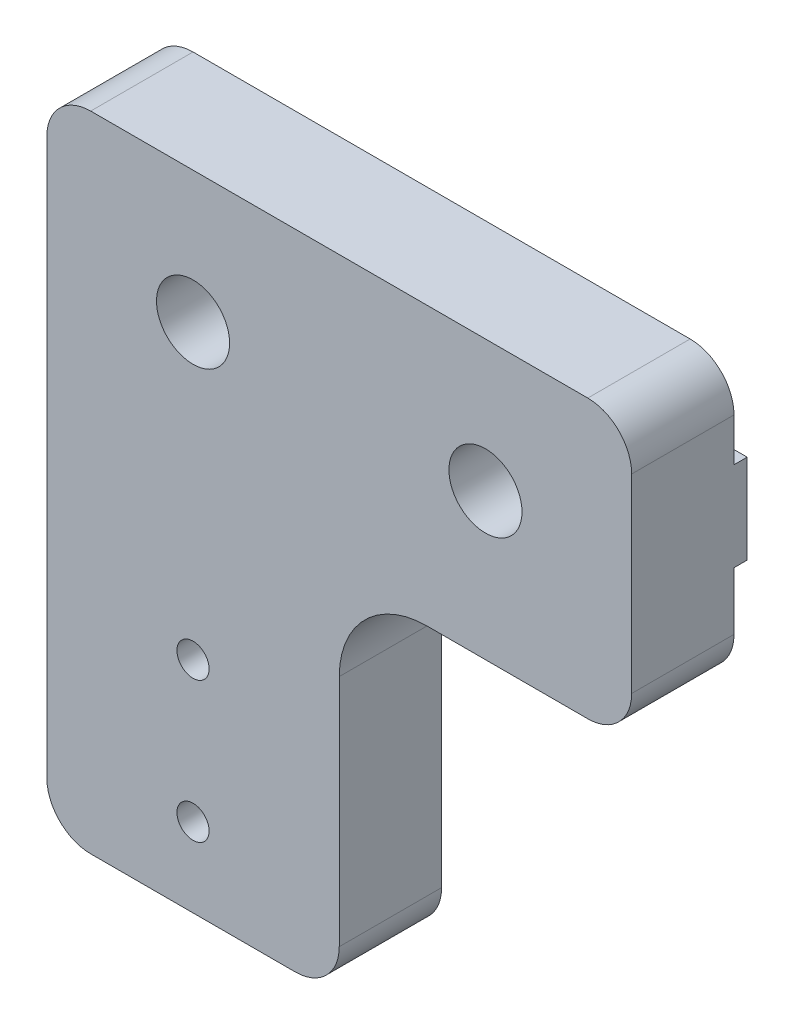
SolidWorks part; units mm, degrees
material "ABS"
ref_plane "Front Plane" through (0, 0, 0) normal (0, 0, 1) x (1, 0, 0)
ref_plane "Top Plane" through (0, 0, 0) normal (0, 1, 0) x (1, 0, 0)
ref_plane "Right Plane" through (0, 0, 0) normal (1, 0, 0) x (0, 0, -1)
sketch "Sketch1" plane through (0, 0, 0) normal (0, 0, 1) x (1, 0, 0)
  line L0 (3, 0) -> (17, 0)
  line L1 (20, 3) -> (20, 19)
  line L2 (26, 25) -> (37, 25)
  line L3 (40, 28) -> (40, 41)
  line L4 (37, 44) -> (3, 44)
  line L5 (0, 41) -> (0, 3)
  line L6 (0, 35) -> (40, 35) construction
  line L7 (20, 25) -> (20, 44) construction
  line L8 (10, 0) -> (10, 44) construction
  circle A0 centre (10, 35) radius 2.5
  circle A1 centre (30, 35) radius 2.5
  circle A2 centre (10, 5.4) radius 1.1
  circle A3 centre (10, 15) radius 1.1
  arc A4 (20, 19) -> (26, 25) centre (26, 19) cw
  arc A5 (37, 25) -> (40, 28) centre (37, 28) ccw
  arc A6 (40, 41) -> (37, 44) centre (37, 41) ccw
  arc A7 (3, 44) -> (0, 41) centre (3, 41) ccw
  arc A8 (0, 3) -> (3, 0) centre (3, 3) ccw
  arc A9 (17, 0) -> (20, 3) centre (17, 3) ccw
  point P26 (40, 25)
  point P29 (40, 44)
  point P32 (0, 44)
  point P35 (0, 0)
  point P38 (20, 0)
  dimension "D5" = 5
  dimension "D6" = 5
  dimension "D7" = 10
  dimension "D8" = 10
  dimension "D10" = 2.2
  dimension "D11" = 2.2
  dimension "D12" = 5.4
  dimension "D13" = 9.6
  dimension "D14" = 6
  dimension "D15" = 3
  dimension "D1" = 44
  dimension "D2" = 20
  dimension "D3" = 40
  dimension "D4" = 19
  dimension "D9" = 9
extrude "Boss-Extrude1" add sketch "Sketch1" along normal blind 7
ref_axis "Axis1" through (30, 35, 7) along (0, 0, -1)
sketch "Sketch2" plane through (40, 0, 0) normal (1, 0, 0) x (0, 0, -1)
  line L0 (0, 28) -> (0, 41) construction
  line L1 (0, 38.05) -> (0.9, 38.05)
  line L2 (0, 38.05) -> (0, 31.95)
  line L3 (0, 31.95) -> (0.9, 31.95)
  line L4 (0.9, 38.05) -> (0.9, 31.95)
  line L5 (-7, 35) -> (0, 35) construction
  point P6 (0, 35)
  dimension "D1" = 6.1
  dimension "D2" = 0.9
extrude "Boss-Extrude2" add sketch "Sketch2" against normal up to surface (40 mm away) contours L3 L4 L1 L2 up to face at (0, 22, 3.5)
sketch "Sketch3" plane through (0, 0, 0) normal (0, 0, 1) x (1, 0, 0)
  circle A0 centre (10, 35) radius 2.5 construction
  circle A1 centre (30, 35) radius 2.5 construction
  circle A2 centre (10, 35) radius 2.5
  circle A3 centre (30, 35) radius 2.5
extrude "Cut-Extrude1" cut sketch "Sketch3" against normal up to next
